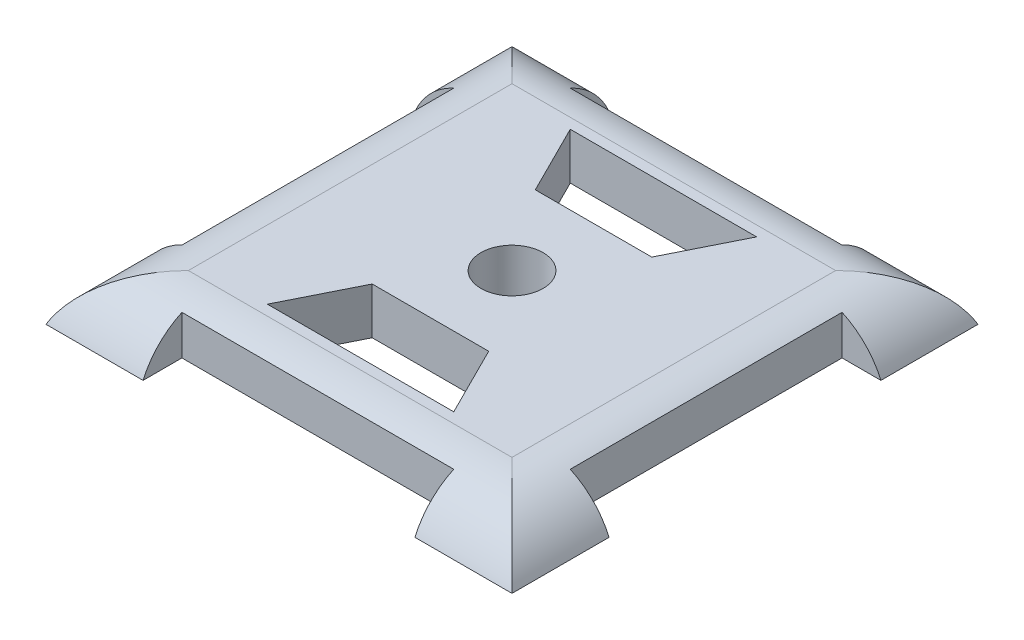
SolidWorks part; units mm, degrees
ref_plane "前视基准面" through (0, 0, 0) normal (0, 0, 1) x (1, 0, 0)
ref_plane "上视基准面" through (0, 0, 0) normal (0, 1, 0) x (1, 0, 0)
ref_plane "右视基准面" through (0, 0, 0) normal (1, 0, 0) x (0, 0, -1)
sketch "草图1" plane through (0, 0, 0) normal (0, 1, 0) x (1, 0, 0)
  line L1 (-10.3316, 12.9847) -> (9.6684, 12.9847)
  line L2 (-10.3316, 12.9847) -> (-10.3316, -7.0153)
  line L3 (-10.3316, -7.0153) -> (9.6684, -7.0153)
  line L4 (9.6684, 12.9847) -> (9.6684, -7.0153)
  dimension "D1" = 20
  dimension "D2" = 20
extrude "凸台-拉伸1" add sketch "草图1" along normal blind 2
sketch "草图2" plane through (0, 2, 0) normal (0, 1, 0) x (1, 0, 0)
  line L0 (-10.3316, 2.9847) -> (11.7316, 2.9847) construction
  line L9 (-10.3316, 12.9847) -> (-10.3316, -7.0153) construction
  line L11 (-4.3316, 9.4847) -> (3.6684, 9.4847)
  line L13 (-2.8316, 6.4847) -> (2.1684, 6.4847)
  line L18 (-0.3316, 9.4847) -> (-0.3316, -0.6377) construction
  line L19 (-4.3316, 9.4847) -> (-2.8316, 6.4847)
  line L20 (3.6684, 9.4847) -> (2.1684, 6.4847)
  line L21 (3.6684, -3.5153) -> (2.1684, -0.5153)
  line L22 (-4.3316, -3.5153) -> (-2.8316, -0.5153)
  line L23 (-2.8316, -0.5153) -> (2.1684, -0.5153)
  line L24 (-4.3316, -3.5153) -> (3.6684, -3.5153)
  point P6 (-0.3316, 6.4847)
  point P15 (-0.3316, -0.5153)
  dimension "D1" = 8
  dimension "D2" = 5
  dimension "D3" = 10
  dimension "D4" = 3.5
  dimension "D5" = 3
extrude "切除-拉伸1" cut sketch "草图2" against normal through all
scale "缩放比例1" scale about centroid uniform scaling yes scale factor 0.6
sketch "草图4" plane through (0, 1.6, 0) normal (0, 1, 0) x (1, 0, 0)
  line L0 (-0.3316, 8.9847) -> (-0.3316, -4.8037) construction
  line L1 (5.6684, 8.9847) -> (-6.3316, 8.9847) construction
  line L2 (-6.3316, 2.9847) -> (7.6227, 2.9847) construction
  line L3 (-6.3316, 8.9847) -> (-6.3316, -3.0153) construction
sketch "草图5" plane through (0, 1.6, 0) normal (0, 1, 0) x (1, 0, 0)
  line L0 (-6.3316, -3.0153) -> (5.6684, -3.0153) construction
  line L1 (-3.8316, -3.0153) -> (3.1684, -3.0153)
  line L2 (-3.8316, -3.0153) -> (-3.8316, -2.0153)
  line L3 (-3.8316, -2.0153) -> (3.1684, -2.0153)
  line L5 (-0.3316, 8.9847) -> (-0.3316, -4.8037) construction
  line L6 (3.1684, -3.0153) -> (3.1684, -2.0153)
  line L7 (-6.3316, 2.9847) -> (7.6227, 2.9847) construction
  line L8 (-5.3316, 6.4847) -> (-5.3316, -0.5153)
  line L9 (-6.3316, -0.5153) -> (-5.3316, -0.5153)
  line L10 (-6.3316, 6.4847) -> (-6.3316, -0.5153)
  line L11 (-6.3316, 6.4847) -> (-5.3316, 6.4847)
  line L12 (3.1684, 7.9847) -> (-3.8316, 7.9847)
  line L13 (-3.8316, 8.9847) -> (-3.8316, 7.9847)
  line L14 (3.1684, 8.9847) -> (-3.8316, 8.9847)
  line L15 (3.1684, 8.9847) -> (3.1684, 7.9847)
  line L16 (4.6684, -0.5153) -> (4.6684, 6.4847)
  line L17 (5.6684, 6.4847) -> (4.6684, 6.4847)
  line L18 (5.6684, -0.5153) -> (5.6684, 6.4847)
  line L19 (5.6684, -0.5153) -> (4.6684, -0.5153)
  line L20 (-0.3316, 2.9847) -> (-3.8316, -2.0153) construction
  point P1 (-0.3316, 2.9847)
  dimension "D1" = 1
  dimension "D2" = 4
  dimension "D3" = 6.1033
extrude "切除-拉伸2" cut sketch "草图5" against normal through all
fillet "圆角1" radius 2 4 edges at (-5.0816, 1.6, -8.9847) (5.6684, 1.6, 1.7653) (-5.0816, 1.6, 3.0153) (-6.3316, 1.6, 1.7653)
sketch "草图6" plane through (0, 0.4, 0) normal (0, -1, 0) x (1, 0, 0)
  line L0 (-0.3316, -8.9847) -> (-0.3316, 4.8037) construction
  line L1 (-6.3316, -2.9847) -> (7.6227, -2.9847) construction
  circle A0 centre (-0.3316, -2.9847) radius 0.8
  dimension "D1" = 1.6
extrude "切除-拉伸3" cut sketch "草图6" against normal through all
